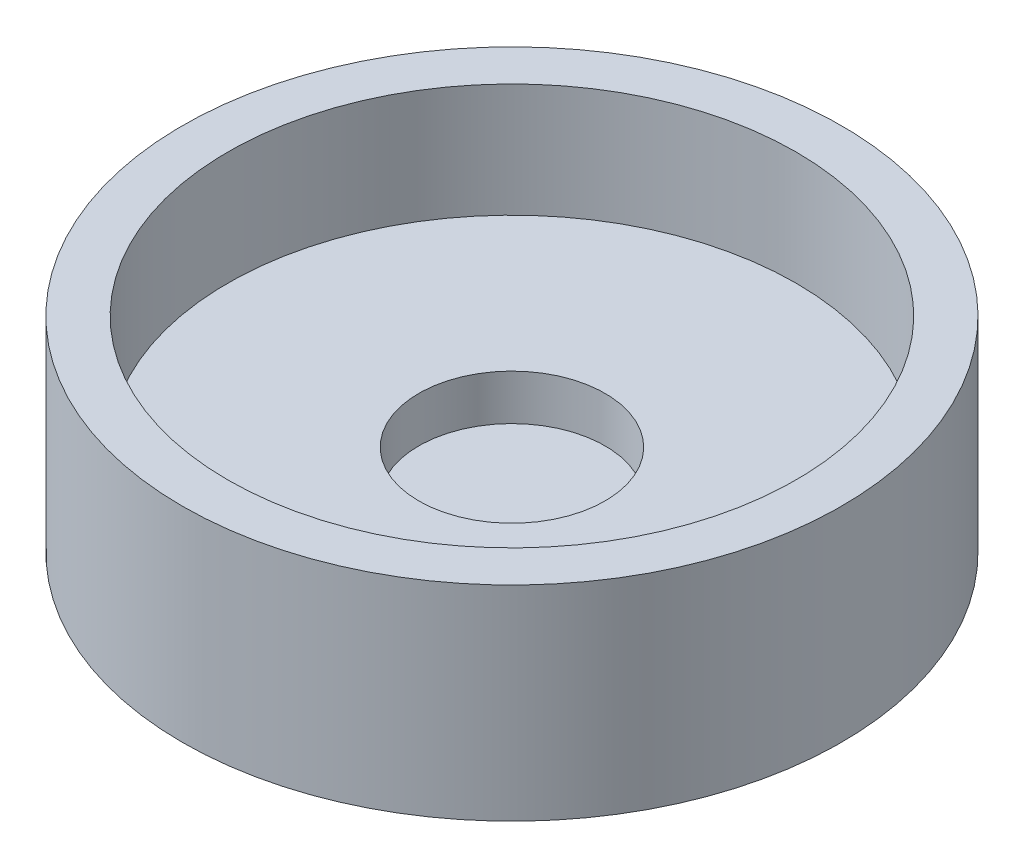
SolidWorks part; units mm, degrees
ref_plane "Front Plane" through (0, 0, 0) normal (0, 0, 1) x (1, 0, 0)
ref_plane "Top Plane" through (0, 0, 0) normal (0, 1, 0) x (1, 0, 0)
ref_plane "Right Plane" through (0, 0, 0) normal (1, 0, 0) x (0, 0, -1)
sketch "Sketch2" plane through (0, 0, 0) normal (0, 1, 0) x (1, 0, 0)
  circle A0 centre (0, 0) radius 12.5
  circle A2 centre (0, 0) radius 14.5
  dimension "D1" = 25
  dimension "D2" = 2
extrude "Boss-Extrude1" add sketch "Sketch2" along normal blind 5
extrude "Boss-Extrude2" add sketch "Sketch2<3>" against normal blind 4 contours A0 | A2 A0 region at (0, 0, 0) region at (-14.0899, 0, 0)
sketch "Sketch2<3>" plane through (0, 0, 0) normal (0, 1, 0) x (1, 0, 0) same geometry as "Sketch2"
sketch "Sketch3" plane through (0, 0, 0) normal (0, 1, 0) x (1, 0, 0)
  circle A0 centre (0, 0) radius 4.1
  dimension "D1" = 8.2
extrude "Cut-Extrude1" cut sketch "Sketch3" against normal blind 2
